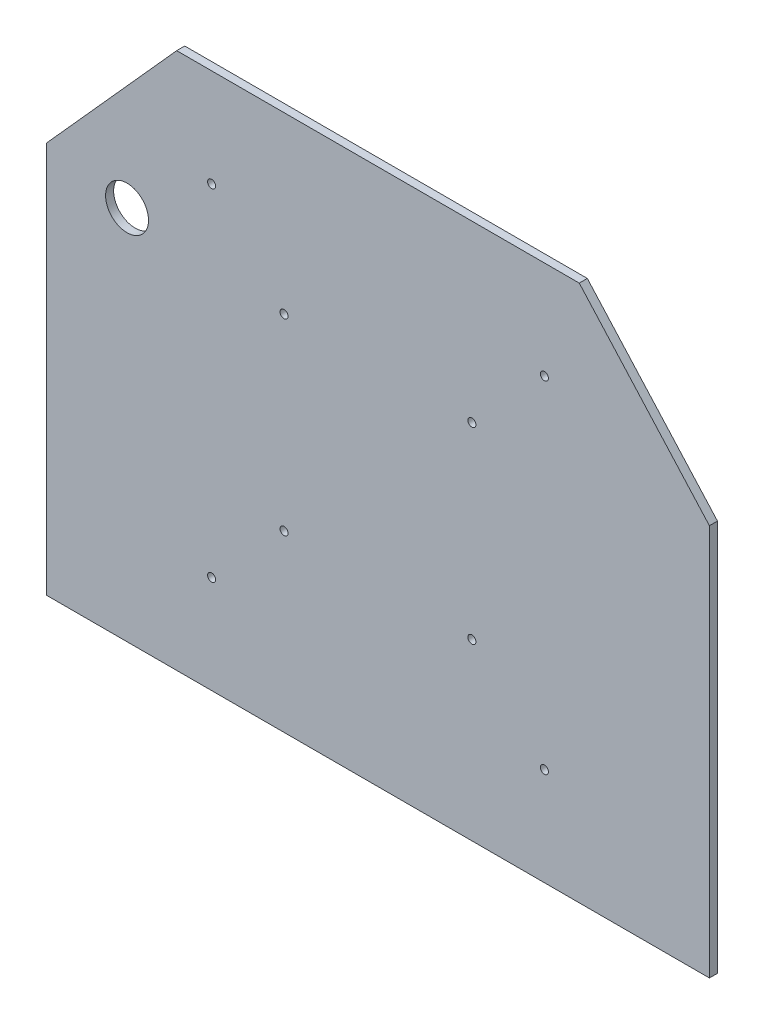
SolidWorks part; units mm, degrees
ref_plane "Plan de face" through (0, 0, 0) normal (0, 0, 1) x (1, 0, 0)
ref_plane "Plan de dessus" through (0, 0, 0) normal (0, 1, 0) x (1, 0, 0)
ref_plane "Plan de droite" through (0, 0, 0) normal (1, 0, 0) x (0, 0, -1)
sketch "Esquisse1" plane through (0, 0, 0) normal (0, 0, 1) x (1, 0, 0)
  line L0 (0, 0) -> (280.2, 0) construction
  line L1 (280.2, 0) -> (280.2, 127.45) construction
  line L2 (280.2, 127.45) -> (215.1, 200) construction
  line L3 (215.1, 200) -> (65.1, 200) construction
  line L4 (65.1, 200) -> (0, 127.45) construction
  line L5 (0, 0) -> (0, 127.45) construction
  line L6 (0, 0) -> (0, 127.45)
  line L7 (0, 127.45) -> (65.1, 200)
  line L8 (65.1, 200) -> (215.1, 200)
  line L9 (215.1, 200) -> (280.2, 127.45)
  line L10 (280.2, 127.45) -> (280.2, 0)
  line L11 (280.2, 0) -> (0, 0)
  point P3 (140.1, 200)
  point P8 (140.1, 0)
  dimension "D1" = 280.2
  dimension "D2" = 200
  dimension "D3" = 127.45
  dimension "D4" = 127.45
  dimension "D5" = 150
extrude "Boss.-Extru.1" add sketch "Esquisse1" along normal blind 3
sketch "Esquisse2" plane through (0, 0, 0) normal (0, 0, -1) x (-1, 0, 0)
  line L1 (-16.6, 252) -> (-16.6, 0) construction
  line L2 (-16.6, 0) -> (-16.6, 145.9694)
  line L3 (-16.6, 0) -> (0, 0)
  line L4 (0, 0) -> (0, 127.45)
  line L5 (0, 127.45) -> (-16.6, 145.9694)
  line L6 (-140.1, 200) -> (-140.1, -18.7191) construction
  line L7 (-215.1, 200) -> (-65.1, 200) construction
  line L8 (-280.2, 127.45) -> (-263.6, 145.9694)
  line L9 (-280.2, 0) -> (-280.2, 127.45)
  line L10 (-263.6, 0) -> (-280.2, 0)
  line L11 (-263.6, 0) -> (-263.6, 145.9694)
extrude "Enlèv. mat.-Extru.1" cut sketch "Esquisse2" against normal through all
sketch "Esquisse3" plane through (0, 0, 3) normal (0, 0, 1) x (1, 0, 0)
  line L0 (140.1, 200) -> (140.1, -25.2955) construction
  line L1 (215.1, 200) -> (65.1, 200) construction
  line L2 (215.1, 200) -> (65.1, 200) construction
  circle A0 centre (78.1, 163.5) radius 1.5
  circle A1 centre (78.1, 36.5) radius 1.5
  circle A2 centre (202.1, 36.5) radius 1.5
  circle A3 centre (202.1, 163.5) radius 1.5
  dimension "D1" = 3
  dimension "D2" = 3
  dimension "D4" = 36.5
  dimension "D3" = 127
  dimension "D5" = 62
extrude "Enlèv. mat.-Extru.2" cut sketch "Esquisse3" against normal through all
sketch "Esquisse4" plane through (0, 0, 3) normal (0, 0, 1) x (1, 0, 0)
  line L0 (16.6, 0) -> (263.6, 0) construction
  line L2 (16.6, 145.9497) -> (16.6, 0) construction
  circle A0 centre (46.6, 140) radius 8
  dimension "D1" = 16
  dimension "D2" = 140
  dimension "D3" = 30
extrude "Enlèv. mat.-Extru.3" cut sketch "Esquisse4" against normal through all
sketch "Esquisse5" plane through (0, 0, 3) normal (0, 0, 1) x (1, 0, 0)
  line L0 (140.1, 249.9536) -> (140.1, 47.0182) construction
  line L1 (2.6642, 100) -> (310.5804, 100) construction
  line L2 (215.1, 200) -> (65.1, 200) construction
  circle A0 centre (105.1, 65) radius 1.5
  circle A1 centre (105.1, 135) radius 1.5
  circle A2 centre (175.1, 135) radius 1.5
  circle A3 centre (175.1, 65) radius 1.5
  point P14 (140.1, 200)
  dimension "D1" = 3
  dimension "D2" = 3
  dimension "D3" = 3
  dimension "D4" = 3
  dimension "D5" = 70
  dimension "D6" = 70
  dimension "D7" = 70
  dimension "D8" = 70
  dimension "D9" = 35
  dimension "D10" = 35
  dimension "D11" = 35
  dimension "D12" = 100
extrude "Enlèv. mat.-Extru.4" cut sketch "Esquisse5" against normal through all
